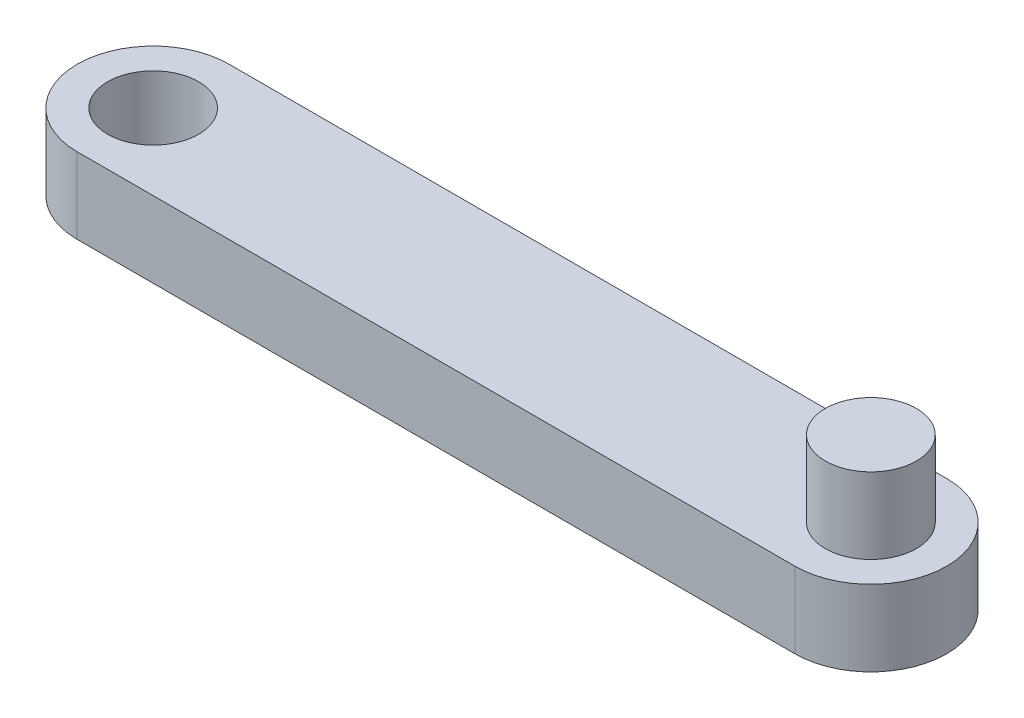
SolidWorks part; units mm, degrees
ref_plane "前视基准面" through (0, 0, 0) normal (0, 0, 1) x (1, 0, 0)
ref_plane "上视基准面" through (0, 0, 0) normal (0, 1, 0) x (1, 0, 0)
ref_plane "右视基准面" through (0, 0, 0) normal (1, 0, 0) x (0, 0, -1)
sketch "草图1" plane through (0, 0, 0) normal (0, 1, 0) x (1, 0, 0)
  line L0 (0, 0) -> (47.28, 0)
  line L2 (47.28, -10) -> (0, -10)
  arc A0 (47.28, -10) -> (47.28, 0) centre (47.28, -5) ccw
  arc A1 (0, 0) -> (0, -10) centre (0, -5) ccw
  circle A2 centre (0, -5) radius 3
  dimension "D1" = 47.28
  dimension "D2" = 5
extrude "凸台-拉伸1" add sketch "草图1" along normal blind 5
sketch "草图2" plane through (0, 5, 0) normal (0, 1, 0) x (1, 0, 0)
  circle A0 centre (47.28, -5) radius 3
extrude "凸台-拉伸2" add sketch "草图2" along normal blind 5
